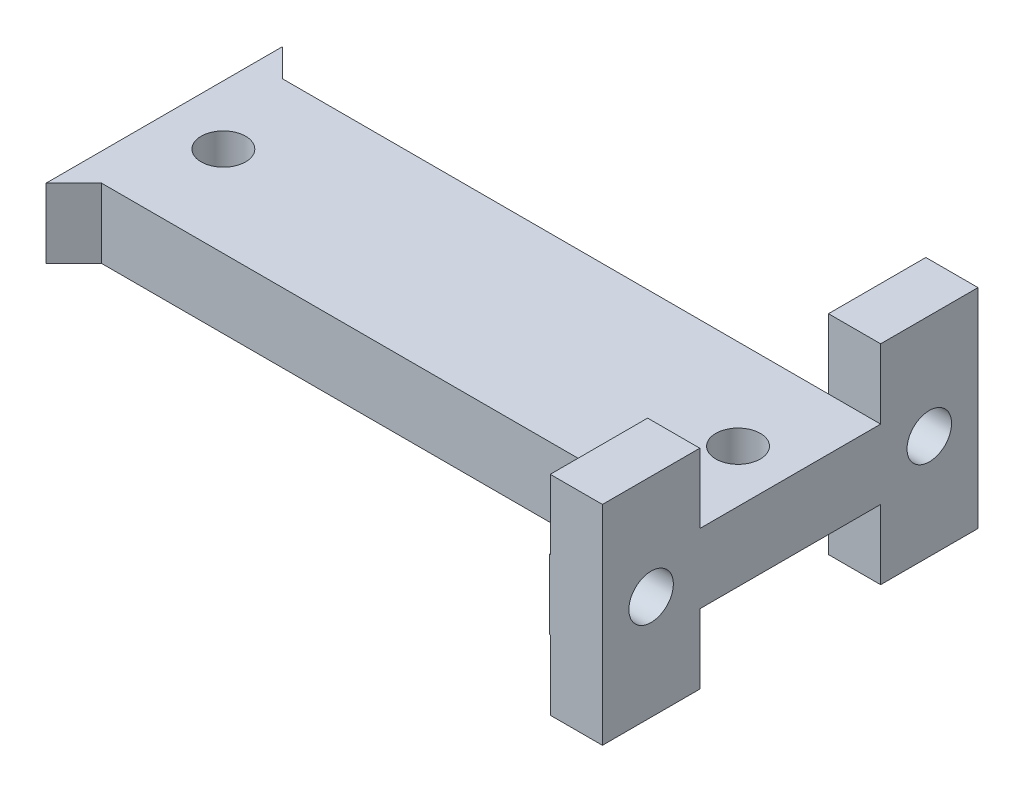
SolidWorks part; units mm, degrees
ref_plane "前视基准面" through (0, 0, 0) normal (0, 0, 1) x (1, 0, 0)
ref_plane "上视基准面" through (0, 0, 0) normal (0, 1, 0) x (1, 0, 0)
ref_plane "右视基准面" through (0, 0, 0) normal (1, 0, 0) x (0, 0, -1)
sketch "草图1" plane through (0, 0, 0) normal (0, 1, 0) x (1, 0, 0)
  line L0 (0, 0) -> (0, -100)
  line L1 (0, 0) -> (100, 0)
  line L2 (100, 0) -> (100, -100)
  line L3 (100, -100) -> (0, -100)
  dimension "D1" = 100
extrude "凸台-拉伸1" add sketch "草图1" along normal blind 10
sketch "草图2" plane through (0, 10, 0) normal (0, 1, 0) x (1, 0, 0)
  line L0 (20.6546, -10.25) -> (20.6546, -13)
  line L1 (20.6546, -13) -> (50.1546, -13)
  line L2 (50.1546, -13) -> (50.1546, -10.25)
  line L3 (50.1546, -10.25) -> (53.9046, -10.25)
  line L4 (16.9046, -2.75) -> (20.6546, -2.75)
  line L5 (20.6546, -2.75) -> (20.6546, 0)
  line L6 (100, 0) -> (0, 0) construction
  line L7 (20.6546, 0) -> (20.6546, -2.75) construction
  line L8 (20.6546, 0) -> (50, 0)
  line L9 (50, 0) -> (50.1546, -2.75)
  line L10 (50.1546, -2.75) -> (53.9046, -2.75)
  line L11 (16.9046, -10.25) -> (20.6546, -10.25)
  line L12 (20.6546, 0) -> (0, 0)
  line L13 (0, 0) -> (0, -100)
  line L14 (0, -100) -> (100, -100)
  line L15 (100, -100) -> (100, 0)
  line L16 (100, 0) -> (50, 0)
  line L17 (20.6546, -13) -> (0, -13)
  line L18 (50.1546, -13) -> (100, -13)
  line L19 (100, -13) -> (100, -100)
  arc A0 (53.9046, -10.25) -> (53.9046, -2.75) centre (53.9046, -6.5) ccw
  arc A1 (16.9046, -2.75) -> (16.9046, -10.25) centre (16.9046, -6.5) ccw
  line M3 (0, -100) -> (100, -100)
  line M4 (100, -100) -> (100, 0)
extrude "切除-拉伸3" cut sketch "草图2" against normal blind 27 contours L18 L1 L17 L13 M3 M4 region at (50, 10, 56.5)
sketch "草图4" plane through (0, 10, 0) normal (0, 1, 0) x (1, 0, 0)
  line L0 (16.9046, -6.5) -> (13.1546, -6.5)
  line L1 (13.1546, -6.5) -> (13.1546, 0)
  line L2 (100, 0) -> (0, 0) construction
  line L3 (13.1546, 0) -> (13.1546, -13)
  line L4 (0, -13) -> (100, -13) construction
  line L5 (53.9046, -6.5) -> (57.6546, -6.5)
  line L6 (57.6546, -6.5) -> (57.6546, -13)
  line L7 (57.6546, -13) -> (57.6546, 0)
  line L8 (57.6546, 0) -> (100, 0)
  line L9 (100, 0) -> (100, -13)
  line L10 (100, -13) -> (57.6546, -13)
  line L11 (13.1546, -13) -> (0, -13)
  line L12 (0, -13) -> (0, 0)
  line L13 (0, 0) -> (13.1546, 0)
  arc A0 (16.9046, -2.75) -> (16.9046, -10.25) centre (16.9046, -6.5) ccw construction
  arc A1 (53.9046, -10.25) -> (53.9046, -2.75) centre (53.9046, -6.5) ccw construction
  line M1 (0, -13) -> (100, -13)
  line M2 (100, -13) -> (100, 0)
  line M3 (100, 0) -> (0, 0)
  line M4 (0, 0) -> (0, -13)
extrude "切除-拉伸4" cut sketch "草图4" against normal blind 27 contours L3 L1 M3 M4 M1 | L7 L6 M1 M2 M3 region at (6.5773, 10, 6.5) region at (78.8273, 10, 6.5)
sketch "草图5" plane through (0, 10, 0) normal (0, 1, 0) x (1, 0, 0)
  circle A0 centre (16.9046, -6.5) radius 1.6
  circle A1 centre (53.9046, -6.5) radius 1.6
extrude "切除-拉伸5" cut sketch "草图5" against normal blind 27
sketch "草图6" plane through (0, 0, 13) normal (0, 0, 1) x (1, 0, 0)
  line L0 (50.1546, 10) -> (50.1546, 0)
  line L1 (13.1546, 10) -> (57.6546, 10) construction
  line L2 (50.1546, 17.2) -> (50.1546, 10) construction
  line L3 (57.6546, 0) -> (13.1546, 0) construction
  line L4 (50.1546, 5) -> (13.1546, 5)
  line L5 (13.1546, 10) -> (13.1546, 0) construction
  line L6 (13.1546, 5) -> (13.1546, 0)
  line L7 (13.1546, 0) -> (50.1546, 0)
  line L8 (50.1546, 5) -> (57.6546, 5)
  line L9 (57.6546, 0) -> (57.6546, 10) construction
  line L10 (57.6546, 5) -> (57.6546, 0)
  line L11 (57.6546, 0) -> (50.1546, 0)
  line M2 (13.1546, 10) -> (13.1546, 0)
  line M3 (13.1546, 0) -> (57.6546, 0)
  line M4 (57.6546, 0) -> (57.6546, 10)
extrude "切除-拉伸6" cut sketch "草图6" against normal blind 27 contours L0 L4 M2 M3 | L8 L0 M3 M4 region at (53.9046, 2.5, 13) region at (31.6546, 2.5, 13)
sketch "草图7" plane through (0, 10, 0) normal (0, 1, 0) x (1, 0, 0)
  line L0 (53.9046, -6.5) -> (53.9046, -13)
  line L1 (13.1546, -13) -> (57.6546, -13) construction
sketch "草图8" plane through (0, 0, 13) normal (0, 0, 1) x (1, 0, 0)
  line L0 (53.8487, 10) -> (53.8487, 5)
  line L1 (13.1546, 10) -> (57.6546, 10) construction
  line L2 (57.6546, 5) -> (13.1546, 5) construction
  line L3 (53.8487, 5) -> (57.6546, 5)
  line L4 (57.6546, 5) -> (57.6546, 10)
  line L5 (57.6546, 10) -> (53.8487, 10)
extrude "凸台-拉伸2" add sketch "草图8" along normal blind 7
sketch "草图9" plane through (0, 10, 0) normal (0, 1, 0) x (1, 0, 0)
  line L0 (53.9046, -6.5) -> (53.9046, 0)
  line L1 (57.6546, 0) -> (13.1546, 0) construction
sketch "草图10" plane through (0, 0, 0) normal (0, 0, -1) x (-1, 0, 0)
  line L0 (-53.9046, 10) -> (-53.9046, 5)
  line L1 (-57.6546, 5) -> (-13.1546, 5) construction
  line L2 (-53.9046, 5) -> (-57.6546, 5)
  line L3 (-57.6546, 5) -> (-57.6546, 10)
  line L4 (-57.6546, 10) -> (-53.9046, 10)
extrude "凸台-拉伸3" add sketch "草图10" along normal blind 7
sketch "草图11" plane through (13.1546, 0, 0) normal (-1, 0, 0) x (0, 0, 1)
  line L0 (6.5, 10) -> (6.5, 5)
  line L1 (6.5, 10) -> (13, 10) construction
  line L2 (6.5, 10) -> (0, 10) construction
  line L3 (0, 5) -> (13, 5) construction
sketch "草图14" plane through (57.6546, 0, 0) normal (1, 0, 0) x (0, 0, -1)
  line L0 (-13, 10) -> (-20, 10)
  line L1 (-20, 10) -> (-20, 15)
  line L2 (-20, 15) -> (-13, 15)
  line L3 (-13, 15) -> (-13, 10)
  line L4 (-20, 5) -> (-20, 0)
  line L5 (-20, 0) -> (-13, 0)
  line L6 (-13, 0) -> (-13, 5)
  line L7 (-13, 5) -> (-20, 5)
  line L8 (0, 10) -> (0, 15)
  line L9 (0, 10) -> (7, 10)
  line L10 (7, 10) -> (7, 15)
  line L11 (7, 15) -> (0, 15)
  line L12 (0, 5) -> (7, 5)
  line L13 (7, 5) -> (7, 0)
  line L14 (7, 0) -> (0, 0)
  line L15 (0, 0) -> (0, 5)
extrude "凸台-拉伸6" add sketch "草图14" against normal up to vertex (3.75 mm away) up to point (53.9046, 10, -7)
sketch "草图15" plane through (53.8487, 0, 0) normal (-1, 0, 0) x (0, 0, 1)
  line L0 (13, 10) -> (20, 5)
  line L1 (6.5, 10) -> (13, 10) construction
  line L2 (13, 10) -> (13, 5) construction
  line L3 (0, 10) -> (0, 5)
  line L4 (0, 5) -> (-7, 5)
  line L5 (-7, 0) -> (-7, 15) construction
  line L6 (-7, 5) -> (-7, 10)
  line L7 (-7, 10) -> (0, 10)
  line L8 (-7, 5) -> (0, 10)
  circle A0 centre (16.5, 7.5) radius 1.6
  circle A1 centre (-3.5, 7.5) radius 1.6
extrude "切除-拉伸8" cut sketch "草图15" against normal up to vertex (3.8059 mm away) contours L8 A1 | L8 A1 | L0 A0 | L0 A0 region at (53.8487, 8.0526, 16.8947) region at (53.8487, 6.9474, 16.1053) region at (53.8487, 6.9474, -3.1053) region at (53.8487, 8.0526, -3.8947) up to point (57.6546, 15, -7)
sketch "草图16" plane through (0, 10, 0) normal (0, 1, 0) x (1, 0, 0)
  line L0 (13.1546, 0) -> (12.6546, 0)
  line L1 (12.6546, 0) -> (12.6546, -13)
  line L2 (13.1546, -13) -> (12.6546, -13)
  line L3 (13.1546, 0) -> (13.1546, -13)
  dimension "D1" = 0.5
extrude "凸台-拉伸7" add sketch "草图16" against normal up to vertex (5 mm away) up to point (13.1546, 5, 13)
sketch "草图17" plane through (0, 5, 0) normal (0, -1, 0) x (1, 0, 0)
  line L0 (12.6546, 13) -> (12.6546, 15)
  line L1 (12.6546, 15) -> (14.6546, 13)
  line L2 (14.6546, 13) -> (12.6546, 13)
  line L3 (53.8487, 13) -> (12.6546, 13) construction
  line L5 (14.6546, 0) -> (12.6546, 0)
  line L6 (12.6546, -2) -> (14.6546, 0)
  line L7 (12.6546, 0) -> (12.6546, -2)
  dimension "D1" = 45
extrude "凸台-拉伸8" add sketch "草图17" against normal up to vertex (5 mm away) up to point (12.6546, 10, 13)
